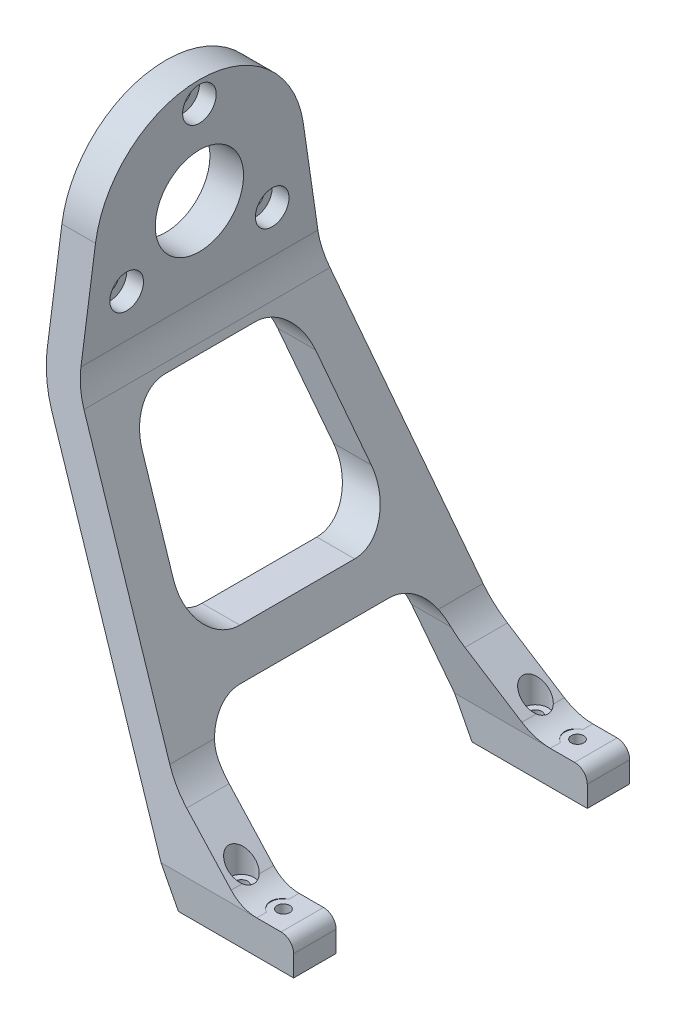
SolidWorks part; units mm, degrees
material "6061 合金"
ref_plane "前视基准面" through (0, 0, 0) normal (0, 0, 1) x (1, 0, 0)
ref_plane "上视基准面" through (0, 0, 0) normal (0, 1, 0) x (1, 0, 0)
ref_plane "右视基准面" through (0, 0, 0) normal (1, 0, 0) x (0, 0, -1)
sketch "草图1" plane through (0, 0, 0) normal (0, 0, 1) x (1, 0, 0)
  line L0 (0, 50) -> (0, 4.8715)
  line L1 (2.2402, -4.3258) -> (41.43, -80)
  line L2 (41.43, -80) -> (66.43, -80)
  arc A0 (2.2402, -4.3258) -> (0, 4.8715) centre (20, 4.8715) cw
  point P7 (0, 0)
  dimension "D5" = 20
  dimension "D1" = 80
  dimension "D2" = 41.43
  dimension "D3" = 50
  dimension "D4" = 25
extrude "拉伸-薄壁1" add sketch "草图1" along normal blind 80 thin thin type mid plane wall 8
sketch "草图8" plane through (0, 0, 0) normal (0, 0, -1) x (-1, 0, 0)
  line L0 (-53.9969, -76) -> (-36.0752, -60.9619)
  line L1 (-43.8631, -76) -> (-66.43, -76) construction
  line L2 (-5.7922, -2.4864) -> (-43.8631, -76) construction
  line L3 (-36.0752, -60.9619) -> (-43.8631, -76)
  line L4 (-43.8631, -76) -> (-53.9969, -76)
  dimension "D1" = 40
  dimension "D2" = 15
extrude "凸台-拉伸1" add sketch "草图8" against normal through all
sketch "草图2" plane through (-4, 0, 0) normal (-1, 0, 0) x (0, 0, 1)
  line L0 (80, 50) -> (0, 50) construction
  line L1 (15.2619, 28.6092) -> (0, -76)
  line L2 (0, -6.1653) -> (0, -84) construction
  line L3 (40, 85.5078) -> (40, -146.0129) construction
  line L4 (80, -84) -> (0, -84) construction
  line L5 (64.7381, 28.6092) -> (80, -76)
  line L9 (0, 50) -> (0, -76)
  line L10 (80, -76) -> (80, 50)
  line L11 (80, 50) -> (0, 50)
  arc A0 (15.2619, 28.6092) -> (64.7381, 28.6092) centre (40, 25) cw
  point P6 (40, 50)
  dimension "D1" = 25
  dimension "D2" = 8
extrude "切除-拉伸1" cut sketch "草图2" against normal through all
fillet "圆角4" radius 10 1 edges at (53.9969, -76, 40)
fillet "圆角5" radius 20 1 edges at (36.0752, -60.9619, 40)
sketch "草图3" plane through (0, -84, 0) normal (0, -1, 0) x (1, 0, 0)
  line L0 (-21.9643, 40) -> (81.8416, 40) construction
  line L1 (66.43, 80) -> (66.43, 0) construction
  line L2 (38.9969, 80) -> (38.9969, 0) construction
  line L3 (38.9969, 80) -> (66.43, 80) construction
  circle A0 centre (48.9969, 75) radius 1.5
  circle A1 centre (58.9969, 75) radius 1.5
  circle A2 centre (58.9969, 5) radius 1.5
  circle A3 centre (48.9969, 5) radius 1.5
  point P9 (66.43, 40)
  dimension "D4" = 3
  dimension "D1" = 10
  dimension "D2" = 10
  dimension "D3" = 5
extrude "切除-拉伸2" cut sketch "草图3" against normal through all
sketch "草图5" plane through (-4, 0, 0) normal (-1, 0, 0) x (0, 0, 1)
  line L0 (10.1059, -84) -> (10.1059, -76)
  line L1 (80, -84) -> (0, -84) construction
  line L2 (10.1059, -76) -> (13.6073, -52)
  line L3 (20.6103, -4) -> (59.3897, -4)
  line L4 (59.3897, -4) -> (65.2255, -44)
  line L5 (69.8941, -76) -> (69.8941, -84)
  line L6 (69.8941, -84) -> (10.1059, -84)
  line L7 (40, 64.2186) -> (40, -117.6272) construction
  line L8 (0, -76) -> (10.1885, -6.1653) construction
  line L9 (14.7745, -44) -> (65.2255, -44)
  line L10 (13.6073, -52) -> (66.3927, -52)
  line L11 (66.3927, -52) -> (69.8941, -76)
  line L12 (14.7745, -44) -> (20.6103, -4)
  dimension "D1" = 10
  dimension "D2" = 80
  dimension "D3" = 8
  dimension "D4" = 8
  dimension "D5" = 40
extrude "切除-拉伸4" cut sketch "草图5" against normal through all
sketch "草图6" plane through (4, 0, 0) normal (1, 0, 0) x (0, 0, -1)
  circle A0 centre (-40, 25) radius 10.5
  circle A1 centre (-40, 45) radius 2
  circle A2 centre (-22.6795, 15) radius 2
  circle A3 centre (-57.3205, 15) radius 2
  point P11 (-40, 25)
  dimension "D1" = 21
  dimension "D3" = 4
  dimension "D2" = 20
  dimension "D4" = 3
extrude "切除-拉伸5" cut sketch "草图6" against normal through all
sketch "草图7" plane through (4, 0, 0) normal (1, 0, 0) x (0, 0, -1)
  circle A0 centre (-40, 45) radius 4
  circle A1 centre (-22.6795, 15) radius 4
  circle A2 centre (-57.3205, 15) radius 4
  dimension "D1" = 8
extrude "切除-拉伸6" cut sketch "草图7" against normal blind 4
fillet "圆角2" radius 10 6 edges at (2.138, -4, 59.3897) (26.9295, -52, 13.6073) (26.9295, -52, 66.3927) (22.7865, -44, 65.2255) (22.7865, -44, 14.7745) (2.138, -4, 20.6103)
fillet "圆角3" radius 3 2 edges at (66.43, -76, 5.0529) (66.43, -76, 74.9471)
ref_plane "基准面1" through (0, -66, 0) normal (0, 1, 0) x (1, 0, 0)
sketch "草图9" plane through (0, -66, 0) normal (0, 1, 0) x (1, 0, 0)
  circle A0 centre (48.9969, -75) radius 3
  circle A1 centre (58.9969, -75) radius 3
  circle A2 centre (58.9969, -5) radius 3
  circle A3 centre (48.9969, -5) radius 3
  dimension "D1" = 6
  dimension "D2" = 6
  dimension "D3" = 6
  dimension "D4" = 6
extrude "切除-拉伸7" cut sketch "草图9" against normal blind 10
